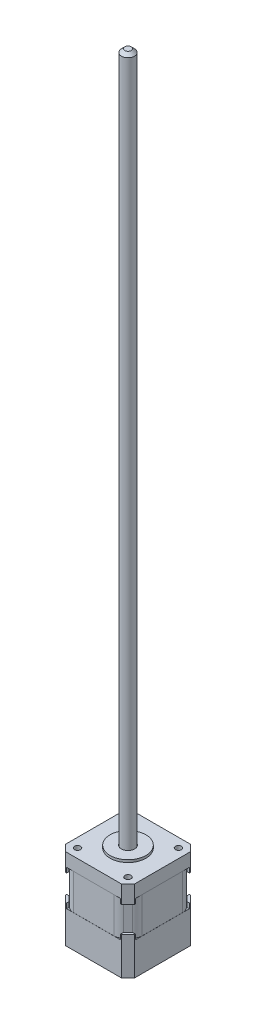
SolidWorks part; units mm, degrees
ref_plane "Plano frontal" through (0, 0, 0) normal (0, 0, 1) x (1, 0, 0)
ref_plane "Plano superior" through (0, 0, 0) normal (0, 1, 0) x (1, 0, 0)
ref_plane "Plano direito" through (0, 0, 0) normal (1, 0, 0) x (0, 0, -1)
other "Centro da massa"
sketch "Esboço1" plane through (0, 0, 0) normal (0, 1, 0) x (1, 0, 0)
  line L1 (-21.15, 21.15) -> (21.15, 21.15)
  line L2 (-21.15, 21.15) -> (-21.15, -21.15)
  line L3 (-21.15, -21.15) -> (21.15, -21.15)
  line L4 (21.15, 21.15) -> (21.15, -21.15)
  line L5 (-21.15, 21.15) -> (21.15, -21.15) construction
  line L6 (-21.15, -21.15) -> (21.15, 21.15) construction
  point P0 (0, 0)
  dimension "D1" = 42.3
  dimension "D2" = 42.3
extrude "UpperBody" add sketch "Esboço1" along normal blind 8
chamfer "Chanfro1" distance 4 angle 45 4 edges at (-21.15, 4, 21.15) (21.15, 4, -21.15) (-21.15, 4, -21.15) (21.15, 4, 21.15)
sketch "Esboço2" plane through (0, 8, 0) normal (0, 1, 0) x (1, 0, 0)
  circle A0 centre (0, 0) radius 11
  circle A1 centre (0, 0) radius 4.1
  dimension "D1" = 22
  dimension "D2" = 8.2
extrude "LittleTopCircle" add sketch "Esboço2" along normal blind 1.5
sketch "Esboço3" plane through (0, 8, 0) normal (0, 1, 0) x (1, 0, 0)
  line L0 (0, 21.15) -> (0, -21.15) construction
  line L1 (17.15, 21.15) -> (-17.15, 21.15) construction
  line L2 (-17.15, -21.15) -> (17.15, -21.15) construction
  line L3 (-21.15, 0) -> (21.15, 0) construction
  line L4 (-21.15, 17.15) -> (-21.15, -17.15) construction
  line L5 (21.15, -17.15) -> (21.15, 17.15) construction
  circle A0 centre (-15.5, 15.5) radius 1.8537
  dimension "D1" = 15.5
  dimension "D2" = 15.5
extrude "MountingHoles" cut sketch "Esboço3" against normal blind 25
pattern_circular "PadrãoCircular1" count 4 over 360 about axis through (0, 8, 0) along (0, 1, 0) of "MountingHoles"
sketch "Esboço7" plane through (0, 0, 0) normal (0, -1, 0) x (1, 0, 0)
  line L8 (-21.15, -16.5287) -> (-19.65, -16.5287)
  line L9 (-21.15, -17.15) -> (-21.15, 17.15) construction
  line L10 (-16.5287, -21.15) -> (-16.5287, -19.65)
  line L11 (17.15, -21.15) -> (-17.15, -21.15) construction
  line L16 (-16.5287, -19.65) -> (16.5287, -19.65)
  line L17 (16.5287, -19.65) -> (19.65, -16.5287)
  line L18 (19.65, -16.5287) -> (19.65, 16.5287)
  line L19 (19.65, 16.5287) -> (16.5287, 19.65)
  line L20 (16.5287, 19.65) -> (-16.5287, 19.65)
  line L21 (-16.5287, 19.65) -> (-19.65, 16.5287)
  line L22 (-19.65, 16.5287) -> (-19.65, -16.5287)
  line L23 (-19.65, -16.5287) -> (-16.5287, -19.65)
  line L24 (-16.5287, -19.65) -> (16.5287, -19.65)
  line L25 (16.5287, -19.65) -> (19.65, -16.5287)
  line L26 (19.65, -16.5287) -> (19.65, 16.5287)
  line L27 (19.65, 16.5287) -> (16.5287, 19.65)
  line L28 (16.5287, 19.65) -> (-16.5287, 19.65)
  line L29 (-16.5287, 19.65) -> (-19.65, 16.5287)
  line L30 (-19.65, 16.5287) -> (-19.65, -16.5287)
  line L31 (-19.65, -16.5287) -> (-16.5287, -19.65)
  line M13 (-17.15, -21.15) -> (17.15, -21.15)
  line M19 (-21.15, 17.15) -> (-21.15, -17.15)
  line M20 (-21.15, -17.15) -> (-17.15, -21.15)
  dimension "D1" = 1.5
extrude "LittleMetalTabs" add sketch "Esboço7" along normal blind 3 contours L31 L30 L8 L10 L24 M19 M20 M13 region at (-18.6471, 0, -18.6471)
pattern_circular "PadrãoCircular2" count 4 over 360 about axis through (0, 9.5, 0) along (0, 1, 0) of "LittleMetalTabs"
sketch "Esboço8" plane through (0, 0, 0) normal (0, -1, 0) x (1, 0, 0)
  line L4 (-14.9, 21.1) -> (14.9, 21.1)
  line L5 (-21.1, 14.9) -> (-21.1, -14.9)
  line L6 (-14.9, -21.1) -> (14.9, -21.1)
  line L7 (21.1, 14.9) -> (21.1, -14.9)
  line L8 (-21.1, 21.1) -> (21.1, -21.1) construction
  line L9 (-21.1, -21.1) -> (21.1, 21.1) construction
  line L10 (-21.1, -14.9) -> (-14.9, -21.1)
  line L11 (-21.1, 14.9) -> (-14.9, 21.1)
  line L12 (14.9, -21.1) -> (21.1, -14.9)
  line L13 (14.9, 21.1) -> (21.1, 14.9)
  point P4 (0, 0)
  dimension "D1" = 42.2
  dimension "D2" = 42.2
extrude "MiddleBody" add sketch "Esboço8" along normal blind 22
fillet "Filete1" radius 6 8 edges at (-21.1, -11, -14.9) (-21.1, -11, 14.9) (-14.9, -11, 21.1) (14.9, -11, 21.1) (-14.9, -11, -21.1) (21.1, -11, 14.9) (14.9, -11, -21.1) (21.1, -11, -14.9)
sketch "Esboço9" plane through (0, -22, 0) normal (0, -1, 0) x (1, 0, 0)
  line L1 (-21.15, -21.15) -> (21.15, -21.15)
  line L2 (-21.15, -21.15) -> (-21.15, 21.15)
  line L3 (-21.15, 21.15) -> (21.15, 21.15)
  line L4 (21.15, -21.15) -> (21.15, 21.15)
  line L5 (-21.15, -21.15) -> (21.15, 21.15) construction
  line L6 (-21.15, 21.15) -> (21.15, -21.15) construction
  point P0 (0, 0)
  dimension "D1" = 42.3
  dimension "D2" = 42.3
extrude "BottomBody" add sketch "Esboço9" along normal blind 8
chamfer "Chanfro5" distance 4 angle 45 4 edges at (21.15, -26, 21.15) (21.15, -26, -21.15) (-21.15, -26, 21.15) (-21.15, -26, -21.15)
sketch "Esboço10" plane through (0, -22, 0) normal (0, 1, 0) x (1, 0, 0)
  line L0 (-16.5287, -19.65) -> (-16.5287, -21.15)
  line L1 (17.15, -21.15) -> (-17.15, -21.15) construction
  line L2 (-19.65, -16.5287) -> (-21.15, -16.5287)
  line L3 (-21.15, -17.15) -> (-21.15, 17.15) construction
  line L16 (-16.5287, -19.65) -> (16.5287, -19.65)
  line L17 (16.5287, -19.65) -> (19.65, -16.5287)
  line L18 (19.65, -16.5287) -> (19.65, 16.5287)
  line L19 (19.65, 16.5287) -> (16.5287, 19.65)
  line L20 (16.5287, 19.65) -> (-16.5287, 19.65)
  line L21 (-16.5287, 19.65) -> (-19.65, 16.5287)
  line L22 (-19.65, 16.5287) -> (-19.65, -16.5287)
  line L23 (-19.65, -16.5287) -> (-16.5287, -19.65)
  line L24 (-16.5287, -19.65) -> (16.5287, -19.65)
  line L25 (16.5287, -19.65) -> (19.65, -16.5287)
  line L26 (19.65, -16.5287) -> (19.65, 16.5287)
  line L27 (19.65, 16.5287) -> (16.5287, 19.65)
  line L28 (16.5287, 19.65) -> (-16.5287, 19.65)
  line L29 (-16.5287, 19.65) -> (-19.65, 16.5287)
  line L30 (-19.65, 16.5287) -> (-19.65, -16.5287)
  line L31 (-19.65, -16.5287) -> (-16.5287, -19.65)
  line M9 (-17.15, -21.15) -> (17.15, -21.15)
  line M15 (-21.15, 17.15) -> (-21.15, -17.15)
  line M16 (-21.15, -17.15) -> (-17.15, -21.15)
  dimension "D1" = 1.5
extrude "LittleMetalTabs2" add sketch "Esboço10" along normal blind 3 contours L31 L2 L0 M15 M16 M9 region at (-18.6471, -22, 18.6471)
ref_point "Ponto2"
ref_axis "Eixo1" through (0, -30, 0) along (0, 1, 0)
pattern_circular "PadrãoCircular3" count 4 over 360 about axis through (0, -30, 0) along (0, 1, 0) of "LittleMetalTabs2"
ref_plane "基准面2" through (0, 8, 0) normal (0, 1, 0) x (1, 0, 0)
sketch "Esboço4" plane through (0, 8, 0) normal (0, 1, 0) x (1, 0, 0)
  circle A0 centre (0, 0) radius 4
  dimension "D1" = 8
extrude "LeadScrew" add sketch "Esboço4" along normal blind 425
chamfer "Chanfro2" distance 2 angle 45 1 edges at (0, 433, 4)
sketch "Esboço5" plane through (0, 433, 0) normal (0, 1, 0) x (1, 0, 0)
  circle A0 centre (0, 0) radius 4 construction
  circle A1 centre (0, 0) radius 4
sketch "Esboço6" plane through (0, 0, 0) normal (1, 0, 0) x (0, 0, -1)
  line L0 (-3, 431.365) -> (-4, 431.6236)
  line L1 (-4, 431.6236) -> (-4, 430.3764)
  line L2 (-4, 430.3764) -> (-3, 430.635)
  line L3 (-3, 430.635) -> (-3, 431.365)
  line L4 (-4, 431.6236) -> (-3, 430.635) construction
  line L5 (-3, 431.365) -> (-4, 430.3764) construction
  line L6 (0, 433) -> (0, 431) construction
  line L7 (2, 433) -> (-2, 433) construction
  line L8 (-4, 431) -> (4, 431) construction
  line L10 (-3, 431) -> (-4, 431) construction
  dimension "D1" = 1
  dimension "D2" = 0.73
  dimension "D3" = 29
sketch "草图1" plane through (-21.1, 0, 0) normal (-1, 0, 0) x (0, 0, 1)
sketch "草图6" plane through (0, -30, 0) normal (0, -1, 0) x (1, 0, 0)
  line L8 (21.15, -17.15) -> (21.15, 17.15)
  line L9 (21.15, 17.15) -> (17.15, 21.15)
  line L10 (17.15, 21.15) -> (-17.15, 21.15)
  line L11 (-17.15, 21.15) -> (-21.15, 17.15)
  line L12 (-21.15, 17.15) -> (-21.15, -17.15)
  line L13 (-21.15, -17.15) -> (-17.15, -21.15)
  line L14 (-17.15, -21.15) -> (17.15, -21.15)
  line L15 (17.15, -21.15) -> (21.15, -17.15)
  line L16 (21.15, -17.15) -> (21.15, 17.15)
  line L17 (21.15, 17.15) -> (17.15, 21.15)
  line L18 (17.15, 21.15) -> (-17.15, 21.15)
  line L19 (-17.15, 21.15) -> (-21.15, 17.15)
  line L20 (-21.15, 17.15) -> (-21.15, -17.15)
  line L21 (-21.15, -17.15) -> (-17.15, -21.15)
  line L22 (-17.15, -21.15) -> (17.15, -21.15)
  line L23 (17.15, -21.15) -> (21.15, -17.15)
  dimension "D1" = 0
extrude "凸台-拉伸1" add sketch "草图6" along normal blind 12
